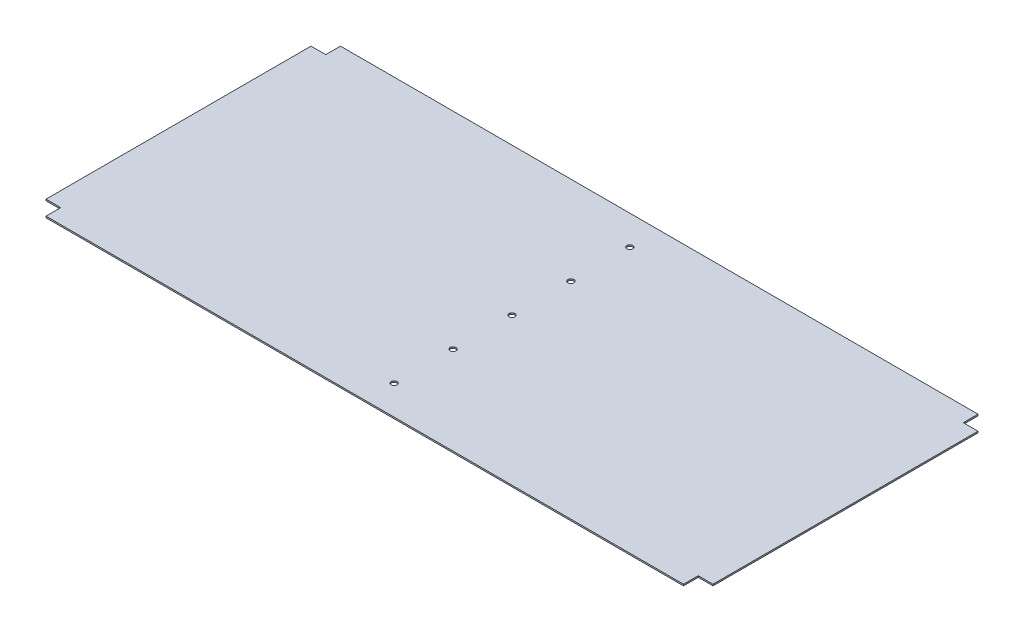
SolidWorks part; units mm, degrees
ref_plane "Ön Düzlem" through (0, 0, 0) normal (0, 0, 1) x (1, 0, 0)
ref_plane "Üst Düzlem" through (0, 0, 0) normal (0, 1, 0) x (1, 0, 0)
ref_plane "Sağ Düzlem" through (0, 0, 0) normal (1, 0, 0) x (0, 0, -1)
sketch "Sketch2" plane through (0, 0, 0) normal (0, 1, 0) x (1, 0, 0)
  line L1 (-453, 0) -> (453, 0)
  line L2 (-453, 0) -> (-453, 400)
  line L3 (-453, 400) -> (453, 400)
  line L4 (453, 0) -> (453, 400)
  point P4 (0, 0)
  dimension "D1" = 906
  dimension "D2" = 400
base flange "Base-Flange1" sketch "Sketch2" thickness 2 reverse thickness direction no parameters "D1"=0.7
sketch "Sketch7" plane through (0, 0, 0) normal (0, 1, 0) x (1, 0, 0)
  line L0 (-453, 200) -> (-378.6198, 200) construction
  line L1 (-453, 400) -> (-433, 400)
  line L2 (-453, 400) -> (-453, 380)
  line L3 (-453, 380) -> (-433, 380)
  line L4 (-433, 400) -> (-433, 380)
  line L5 (-453, 400) -> (-453, 0) construction
  line L6 (0, 400) -> (0, 319.6069) construction
  line L7 (453, 400) -> (-453, 400) construction
  line L8 (-453, 20) -> (-433, 20)
  line L9 (-433, 0) -> (-433, 20)
  line L10 (-453, 0) -> (-433, 0)
  line L11 (-453, 0) -> (-453, 20)
  line L12 (453, 0) -> (453, 20)
  line L13 (453, 0) -> (433, 0)
  line L14 (433, 0) -> (433, 20)
  line L15 (453, 20) -> (433, 20)
  line L16 (433, 400) -> (433, 380)
  line L17 (453, 380) -> (433, 380)
  line L18 (453, 400) -> (453, 380)
  line L19 (453, 400) -> (433, 400)
  dimension "D1" = 20
extrude "Cut-Extrude1" cut sketch "Sketch7" against normal blind 10 normal cut yes
sketch "Sketch8" plane through (0, 0, 0) normal (0, 1, 0) x (1, 0, 0)
  line L0 (433, 400) -> (-433, 400) construction
  line L1 (-433, 0) -> (433, 0) construction
  line L2 (453, 20) -> (453, 380) construction
  circle A0 centre (0, 360) radius 4
  circle A1 centre (0, 280) radius 4
  circle A2 centre (0, 200) radius 4
  circle A3 centre (0, 120) radius 4
  circle A4 centre (0, 40) radius 4
  point P14 (0, 0)
  dimension "D1" = 8
  dimension "D3" = 40
  dimension "D4" = 40
  dimension "D5" = 453
  dimension "D2" = 5
extrude "Cut-Extrude2" cut sketch "Sketch8" against normal blind 10 normal cut yes
sketch "Büküm-Çizgileri1" [suppressed] plane through (0, 0, 0) normal (0, 1, 0) x (1, 0, 0)
sketch "Sınırlandırma-Kutusu1" [suppressed] plane through (0, 0, 0) normal (0, 1, 0) x (1, 0, 0)
sheet metal parameters "Sac-Levha1" thickness 2 parameters "D1"=0.7
flat pattern "Düz-Çoğaltma1" [suppressed]
sketch "Büküm-Çizgileri2" plane through (0, 0, 0) normal (0, 1, 0) x (1, 0, 0)
sketch3d "Sınırlandırma-Kutusu2" [suppressed]
  line L0 (-453, 400, 0) -> (453, 400, 0) construction
  line L1 (-453, 0, 0) -> (453, 0, 0) construction
  line L2 (-453, 400, 0) -> (-453, 0, 0) construction
  line L3 (453, 400, 0) -> (453, 0, 0) construction
sheet metal parameters "Sac-Levha2" thickness 2 parameters "D1"=0.7
flat pattern "Düz-Çoğaltma1"
sketch "Büküm-Çizgileri2" plane through (0, 0, 0) normal (0, 1, 0) x (1, 0, 0)
sketch3d "Sınırlandırma-Kutusu2" [suppressed]
  line L0 (453, 400, 0) -> (-453, 400, 0) construction
  line L1 (453, 0, 0) -> (-453, 0, 0) construction
  line L2 (453, 400, 0) -> (453, 0, 0) construction
  line L3 (-453, 400, 0) -> (-453, 0, 0) construction
sheet metal parameters "Sac-Levha3" thickness 2 parameters "D1"=0.7
flat pattern "Düz-Çoğaltma1"
sketch "Büküm-Çizgileri2" plane through (0, 0, 0) normal (0, 1, 0) x (1, 0, 0)
sketch3d "Sınırlandırma-Kutusu2" [suppressed]
  line L0 (453, 400, 0) -> (-453, 400, 0) construction
  line L1 (453, 0, 0) -> (-453, 0, 0) construction
  line L2 (453, 400, 0) -> (453, 0, 0) construction
  line L3 (-453, 400, 0) -> (-453, 0, 0) construction
